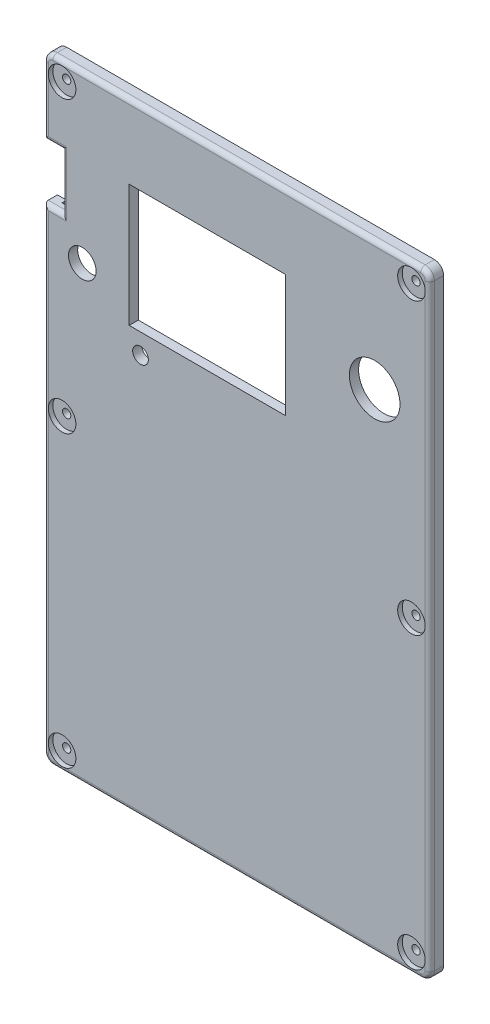
SolidWorks part; units mm, degrees
ref_plane "Front Plane" through (0, 0, 0) normal (0, 0, 1) x (1, 0, 0)
ref_plane "Top Plane" through (0, 0, 0) normal (0, 1, 0) x (1, 0, 0)
ref_plane "Right Plane" through (0, 0, 0) normal (1, 0, 0) x (0, 0, -1)
sketch "Sketch3" plane through (0, 0, 0) normal (0, 0, 1) x (1, 0, 0)
  line L9 (2.54, -170.18) -> (104.14, -170.18)
  line L10 (106.68, -167.64) -> (106.68, -2.54)
  line L11 (104.14, 0) -> (2.54, 0)
  line L17 (104.14, -10.8999) -> (104.14, -79.2701)
  line L19 (104.14, -90.9099) -> (104.14, -159.2801)
  line L21 (10.8999, -167.64) -> (95.7801, -167.64)
  line L23 (2.54, -90.9099) -> (2.54, -159.2801)
  line L25 (2.54, -10.8999) -> (2.54, -79.2701)
  line L27 (10.8999, -2.54) -> (95.7801, -2.54)
  line L43 (2.54, -79.2701) -> (2.54, -10.8999)
  line L47 (0, -2.54) -> (0, -167.64)
  line L53 (10.8999, -2.54) -> (95.7801, -2.54)
  line L55 (104.14, -10.8999) -> (104.14, -79.2701)
  line L57 (104.14, -90.9099) -> (104.14, -159.2801)
  line L59 (95.7801, -167.64) -> (10.8999, -167.64)
  line L61 (2.54, -159.2801) -> (2.54, -90.9099)
  circle A1 centre (5.08, -5.08) radius 1.143
  circle A3 centre (101.6, -5.08) radius 1.143
  arc A8 (0, -167.64) -> (2.54, -170.18) centre (2.54, -167.64) ccw
  arc A9 (104.14, -170.18) -> (106.68, -167.64) centre (104.14, -167.64) ccw
  arc A10 (106.68, -2.54) -> (104.14, 0) centre (104.14, -2.54) ccw
  arc A11 (2.54, 0) -> (0, -2.54) centre (2.54, -2.54) ccw
  circle A13 centre (101.6, -165.1) radius 1.143
  circle A15 centre (5.08, -165.1) radius 1.143
  circle A17 centre (5.08, -85.09) radius 1.143
  circle A19 centre (101.6, -85.09) radius 1.143
  arc A29 (97.8044, -4.7487) -> (95.7801, -2.54) centre (95.7801, -4.572) ccw
  arc A31 (97.8044, -4.7487) -> (101.9313, -8.8756) centre (101.6, -5.08) ccw
  arc A33 (104.14, -10.8999) -> (101.9313, -8.8756) centre (102.108, -10.8999) ccw
  arc A35 (101.9313, -81.2944) -> (101.9313, -88.8856) centre (101.6, -85.09) ccw
  arc A37 (101.9313, -81.2944) -> (104.14, -79.2701) centre (102.108, -79.2701) ccw
  arc A39 (104.14, -90.9099) -> (101.9313, -88.8856) centre (102.108, -90.9099) ccw
  arc A41 (101.9313, -161.3044) -> (104.14, -159.2801) centre (102.108, -159.2801) ccw
  arc A43 (101.9313, -161.3044) -> (97.8044, -165.4313) centre (101.6, -165.1) ccw
  arc A45 (95.7801, -167.64) -> (97.8044, -165.4313) centre (95.7801, -165.608) ccw
  arc A47 (8.8756, -165.4313) -> (10.8999, -167.64) centre (10.8999, -165.608) ccw
  arc A49 (8.8756, -165.4313) -> (4.7487, -161.3044) centre (5.08, -165.1) ccw
  arc A51 (2.54, -159.2801) -> (4.7487, -161.3044) centre (4.572, -159.2801) ccw
  arc A53 (4.7487, -88.8856) -> (2.54, -90.9099) centre (4.572, -90.9099) ccw
  arc A55 (4.7487, -88.8856) -> (4.7487, -81.2944) centre (5.08, -85.09) ccw
  arc A57 (2.54, -79.2701) -> (4.7487, -81.2944) centre (4.572, -79.2701) ccw
  arc A59 (4.7487, -8.8756) -> (8.8756, -4.7487) centre (5.08, -5.08) ccw
  arc A61 (4.7487, -8.8756) -> (2.54, -10.8999) centre (4.572, -10.8999) ccw
  arc A63 (10.8999, -2.54) -> (8.8756, -4.7487) centre (10.8999, -4.572) ccw
  arc A87 (4.7487, -8.8756) -> (2.54, -10.8999) centre (4.572, -10.8999) ccw
  arc A89 (4.7487, -8.8756) -> (8.8756, -4.7487) centre (5.08, -5.08) ccw
  arc A91 (10.8999, -2.54) -> (8.8756, -4.7487) centre (10.8999, -4.572) ccw
  arc A93 (97.8044, -4.7487) -> (95.7801, -2.54) centre (95.7801, -4.572) ccw
  arc A95 (97.8044, -4.7487) -> (101.9313, -8.8756) centre (101.6, -5.08) ccw
  arc A97 (104.14, -10.8999) -> (101.9313, -8.8756) centre (102.108, -10.8999) ccw
  arc A99 (101.9313, -81.2944) -> (104.14, -79.2701) centre (102.108, -79.2701) ccw
  arc A101 (101.9313, -81.2944) -> (101.9313, -88.8856) centre (101.6, -85.09) ccw
  arc A103 (104.14, -90.9099) -> (101.9313, -88.8856) centre (102.108, -90.9099) ccw
  arc A105 (101.9313, -161.3044) -> (104.14, -159.2801) centre (102.108, -159.2801) ccw
  arc A107 (101.9313, -161.3044) -> (97.8044, -165.4313) centre (101.6, -165.1) ccw
  arc A109 (95.7801, -167.64) -> (97.8044, -165.4313) centre (95.7801, -165.608) ccw
  arc A111 (8.8756, -165.4313) -> (10.8999, -167.64) centre (10.8999, -165.608) ccw
  arc A113 (8.8756, -165.4313) -> (4.7487, -161.3044) centre (5.08, -165.1) ccw
  arc A115 (2.54, -159.2801) -> (4.7487, -161.3044) centre (4.572, -159.2801) ccw
  arc A117 (4.7487, -88.8856) -> (2.54, -90.9099) centre (4.572, -90.9099) ccw
  arc A119 (4.7487, -88.8856) -> (4.7487, -81.2944) centre (5.08, -85.09) ccw
  arc A121 (2.54, -79.2701) -> (4.7487, -81.2944) centre (4.572, -79.2701) ccw
  dimension "D1" = 2.286
  dimension "D2" = 2.286
  dimension "D3" = 2.286
  dimension "D4" = 2.286
  dimension "D5" = 2.286
  dimension "D6" = 2.286
extrude "Boss-Extrude3" add sketch "Sketch3" along normal blind 3.81 contours L27 A63 A59 A61 L25 A57 A55 A53 L23 A51 A49 A47 L21 A45 A43 A41 L19 A39 A35 A37 L17 A33 A31 A29 | L11 A11 L47 A8 L9 A9 L10 A10 A63 L27 A29 A31 A33 L17 A37 A35 A39 L19 A41 A43 A45 L21 A47 A49 A51 L23 A53 A55 A57 L25 A61 A59 A19 A17 A15 A13 A1 A3 region at (2.1642, -168.0158, 0) region at (53.34, -85.09, 0)
sketch "Sketch7" plane through (0, 0, 0) normal (0, 0, -1) x (-1, 0, 0)
  line L0 (-106.68, -167.64) -> (-106.68, -2.54) construction
  line L1 (-104.14, -170.18) -> (-2.54, -170.18)
  line L2 (0, -167.64) -> (0, -2.54)
  line L3 (-2.54, 0) -> (-104.14, 0)
  line L4 (-2.54, -10.8999) -> (-2.54, -79.2701)
  line L5 (-2.54, -90.9099) -> (-2.54, -159.2801)
  line L6 (-95.7801, -167.64) -> (-10.8999, -167.64)
  line L7 (-104.14, -90.9099) -> (-104.14, -159.2801)
  line L9 (-95.7801, -2.54) -> (-10.8999, -2.54)
  line L11 (-104.14, -79.2701) -> (-104.14, -36.5576)
  line L13 (-106.68, -2.54) -> (-106.68, -167.64)
  line L14 (-104.14, -36.5576) -> (-104.14, -10.8999)
  line L16 (-95.7801, -2.54) -> (-10.8999, -2.54)
  line L17 (-2.54, -10.8999) -> (-2.54, -79.2701)
  line L18 (-2.54, -90.9099) -> (-2.54, -159.2801)
  line L19 (-10.8999, -167.64) -> (-95.7801, -167.64)
  line L20 (-104.14, -159.2801) -> (-104.14, -90.9099)
  line L21 (-106.68, -21.336) -> (-104.14, -21.336)
  line L22 (-104.14, -36.5576) -> (-106.68, -36.5576)
  circle A0 centre (-101.6, -5.08) radius 0.9525
  circle A1 centre (-5.08, -5.08) radius 0.9525
  arc A2 (-106.68, -167.64) -> (-104.14, -170.18) centre (-104.14, -167.64) ccw
  arc A3 (-2.54, -170.18) -> (0, -167.64) centre (-2.54, -167.64) ccw
  arc A4 (0, -2.54) -> (-2.54, 0) centre (-2.54, -2.54) ccw
  arc A5 (-104.14, 0) -> (-106.68, -2.54) centre (-104.14, -2.54) ccw
  circle A6 centre (-5.08, -165.1) radius 0.9525
  circle A7 centre (-101.6, -165.1) radius 0.9525
  circle A8 centre (-101.6, -85.09) radius 0.9525
  circle A9 centre (-5.08, -85.09) radius 0.9525
  arc A10 (-8.8756, -4.7487) -> (-10.8999, -2.54) centre (-10.8999, -4.572) ccw
  arc A11 (-8.8756, -4.7487) -> (-4.7487, -8.8756) centre (-5.08, -5.08) ccw
  arc A12 (-2.54, -10.8999) -> (-4.7487, -8.8756) centre (-4.572, -10.8999) ccw
  arc A13 (-4.7487, -81.2944) -> (-4.7487, -88.8856) centre (-5.08, -85.09) ccw
  arc A14 (-4.7487, -81.2944) -> (-2.54, -79.2701) centre (-4.572, -79.2701) ccw
  arc A15 (-2.54, -90.9099) -> (-4.7487, -88.8856) centre (-4.572, -90.9099) ccw
  arc A16 (-4.7487, -161.3044) -> (-2.54, -159.2801) centre (-4.572, -159.2801) ccw
  arc A17 (-4.7487, -161.3044) -> (-8.8756, -165.4313) centre (-5.08, -165.1) ccw
  arc A18 (-10.8999, -167.64) -> (-8.8756, -165.4313) centre (-10.8999, -165.608) ccw
  arc A19 (-97.8044, -165.4313) -> (-95.7801, -167.64) centre (-95.7801, -165.608) ccw
  arc A20 (-97.8044, -165.4313) -> (-101.9313, -161.3044) centre (-101.6, -165.1) ccw
  arc A21 (-104.14, -159.2801) -> (-101.9313, -161.3044) centre (-102.108, -159.2801) ccw
  arc A22 (-101.9313, -88.8856) -> (-104.14, -90.9099) centre (-102.108, -90.9099) ccw
  arc A23 (-101.9313, -88.8856) -> (-101.9313, -81.2944) centre (-101.6, -85.09) ccw
  arc A24 (-104.14, -79.2701) -> (-101.9313, -81.2944) centre (-102.108, -79.2701) ccw
  arc A25 (-101.9313, -8.8756) -> (-97.8044, -4.7487) centre (-101.6, -5.08) ccw
  arc A26 (-101.9313, -8.8756) -> (-104.14, -10.8999) centre (-102.108, -10.8999) ccw
  arc A27 (-95.7801, -2.54) -> (-97.8044, -4.7487) centre (-95.7801, -4.572) ccw
  arc A28 (-101.9313, -8.8756) -> (-104.14, -10.8999) centre (-102.108, -10.8999) ccw
  arc A29 (-101.9313, -8.8756) -> (-97.8044, -4.7487) centre (-101.6, -5.08) ccw
  arc A30 (-95.7801, -2.54) -> (-97.8044, -4.7487) centre (-95.7801, -4.572) ccw
  arc A31 (-8.8756, -4.7487) -> (-10.8999, -2.54) centre (-10.8999, -4.572) ccw
  arc A32 (-8.8756, -4.7487) -> (-4.7487, -8.8756) centre (-5.08, -5.08) ccw
  arc A33 (-2.54, -10.8999) -> (-4.7487, -8.8756) centre (-4.572, -10.8999) ccw
  arc A34 (-4.7487, -81.2944) -> (-2.54, -79.2701) centre (-4.572, -79.2701) ccw
  arc A35 (-4.7487, -81.2944) -> (-4.7487, -88.8856) centre (-5.08, -85.09) ccw
  arc A36 (-2.54, -90.9099) -> (-4.7487, -88.8856) centre (-4.572, -90.9099) ccw
  arc A37 (-4.7487, -161.3044) -> (-2.54, -159.2801) centre (-4.572, -159.2801) ccw
  arc A38 (-4.7487, -161.3044) -> (-8.8756, -165.4313) centre (-5.08, -165.1) ccw
  arc A39 (-10.8999, -167.64) -> (-8.8756, -165.4313) centre (-10.8999, -165.608) ccw
  arc A40 (-97.8044, -165.4313) -> (-95.7801, -167.64) centre (-95.7801, -165.608) ccw
  arc A41 (-97.8044, -165.4313) -> (-101.9313, -161.3044) centre (-101.6, -165.1) ccw
  arc A42 (-104.14, -159.2801) -> (-101.9313, -161.3044) centre (-102.108, -159.2801) ccw
  arc A43 (-101.9313, -88.8856) -> (-104.14, -90.9099) centre (-102.108, -90.9099) ccw
  arc A44 (-101.9313, -88.8856) -> (-101.9313, -81.2944) centre (-101.6, -85.09) ccw
  arc A45 (-104.14, -79.2701) -> (-101.9313, -81.2944) centre (-102.108, -79.2701) ccw
extrude "Cut-Extrude9" cut sketch "Sketch7" against normal blind 1.27 contours L9 A27 A25 A26 L14 L11 A24 A23 A22 L7 A21 A20 A19 L6 A18 A17 A16 L5 A15 A13 A14 L4 A12 A11 A10 region at (53.34, -85.09, 0)
sketch "Sketch10" plane through (0, 0, 3.81) normal (0, 0, 1) x (1, 0, 0)
  line L0 (0, -2.54) -> (0, -21.336)
  line L1 (2.54, -170.18) -> (104.14, -170.18)
  line L2 (106.68, -167.64) -> (106.68, -2.54)
  line L3 (104.14, 0) -> (2.54, 0)
  line L4 (104.14, -10.8999) -> (104.14, -79.2701)
  line L5 (104.14, -90.9099) -> (104.14, -159.2801)
  line L6 (10.8999, -167.64) -> (95.7801, -167.64)
  line L7 (2.54, -90.9099) -> (2.54, -159.2801)
  line L8 (2.54, -36.576) -> (2.54, -79.2701)
  line L9 (10.8999, -2.54) -> (95.7801, -2.54)
  line L10 (2.54, -10.8999) -> (2.54, -21.336)
  line L11 (2.54, -79.2701) -> (2.54, -36.576)
  line L12 (2.54, -36.576) -> (0, -36.576)
  line L13 (0, -36.576) -> (0, -167.64)
  line L14 (0, -21.336) -> (2.54, -21.336)
  line L15 (2.54, -21.336) -> (2.54, -10.8999)
  line L16 (10.8999, -2.54) -> (95.7801, -2.54)
  line L17 (104.14, -10.8999) -> (104.14, -79.2701)
  line L18 (104.14, -90.9099) -> (104.14, -159.2801)
  line L19 (95.7801, -167.64) -> (10.8999, -167.64)
  line L20 (2.54, -159.2801) -> (2.54, -90.9099)
  line L22 (0, -21.336) -> (5.08, -21.336)
  line L23 (0, -21.336) -> (0, -36.576)
  line L24 (0, -36.576) -> (5.08, -36.576)
  line L25 (5.08, -21.336) -> (5.08, -36.576)
  circle A0 centre (5.08, -5.08) radius 0.9525
  circle A1 centre (101.6, -5.08) radius 0.9525
  arc A2 (0, -167.64) -> (2.54, -170.18) centre (2.54, -167.64) ccw
  arc A3 (104.14, -170.18) -> (106.68, -167.64) centre (104.14, -167.64) ccw
  arc A4 (106.68, -2.54) -> (104.14, 0) centre (104.14, -2.54) ccw
  arc A5 (2.54, 0) -> (0, -2.54) centre (2.54, -2.54) ccw
  circle A6 centre (101.6, -165.1) radius 0.9525
  circle A7 centre (5.08, -165.1) radius 0.9525
  circle A8 centre (5.08, -85.09) radius 0.9525
  circle A9 centre (101.6, -85.09) radius 0.9525
  arc A10 (97.8044, -4.7487) -> (95.7801, -2.54) centre (95.7801, -4.572) ccw
  arc A11 (97.8044, -4.7487) -> (101.9313, -8.8756) centre (101.6, -5.08) ccw
  arc A12 (104.14, -10.8999) -> (101.9313, -8.8756) centre (102.108, -10.8999) ccw
  arc A13 (101.9313, -81.2944) -> (101.9313, -88.8856) centre (101.6, -85.09) ccw
  arc A14 (101.9313, -81.2944) -> (104.14, -79.2701) centre (102.108, -79.2701) ccw
  arc A15 (104.14, -90.9099) -> (101.9313, -88.8856) centre (102.108, -90.9099) ccw
  arc A16 (101.9313, -161.3044) -> (104.14, -159.2801) centre (102.108, -159.2801) ccw
  arc A17 (101.9313, -161.3044) -> (97.8044, -165.4313) centre (101.6, -165.1) ccw
  arc A18 (95.7801, -167.64) -> (97.8044, -165.4313) centre (95.7801, -165.608) ccw
  arc A19 (8.8756, -165.4313) -> (10.8999, -167.64) centre (10.8999, -165.608) ccw
  arc A20 (8.8756, -165.4313) -> (4.7487, -161.3044) centre (5.08, -165.1) ccw
  arc A21 (2.54, -159.2801) -> (4.7487, -161.3044) centre (4.572, -159.2801) ccw
  arc A22 (4.7487, -88.8856) -> (2.54, -90.9099) centre (4.572, -90.9099) ccw
  arc A23 (4.7487, -88.8856) -> (4.7487, -81.2944) centre (5.08, -85.09) ccw
  arc A24 (2.54, -79.2701) -> (4.7487, -81.2944) centre (4.572, -79.2701) ccw
  arc A25 (4.7487, -8.8756) -> (8.8756, -4.7487) centre (5.08, -5.08) ccw
  arc A26 (4.7487, -8.8756) -> (2.54, -10.8999) centre (4.572, -10.8999) ccw
  arc A27 (10.8999, -2.54) -> (8.8756, -4.7487) centre (10.8999, -4.572) ccw
  arc A28 (4.7487, -8.8756) -> (2.54, -10.8999) centre (4.572, -10.8999) ccw
  arc A29 (4.7487, -8.8756) -> (8.8756, -4.7487) centre (5.08, -5.08) ccw
  arc A30 (10.8999, -2.54) -> (8.8756, -4.7487) centre (10.8999, -4.572) ccw
  arc A31 (97.8044, -4.7487) -> (95.7801, -2.54) centre (95.7801, -4.572) ccw
  arc A32 (97.8044, -4.7487) -> (101.9313, -8.8756) centre (101.6, -5.08) ccw
  arc A33 (104.14, -10.8999) -> (101.9313, -8.8756) centre (102.108, -10.8999) ccw
  arc A34 (101.9313, -81.2944) -> (104.14, -79.2701) centre (102.108, -79.2701) ccw
  arc A35 (101.9313, -81.2944) -> (101.9313, -88.8856) centre (101.6, -85.09) ccw
  arc A36 (104.14, -90.9099) -> (101.9313, -88.8856) centre (102.108, -90.9099) ccw
  arc A37 (101.9313, -161.3044) -> (104.14, -159.2801) centre (102.108, -159.2801) ccw
  arc A38 (101.9313, -161.3044) -> (97.8044, -165.4313) centre (101.6, -165.1) ccw
  arc A39 (95.7801, -167.64) -> (97.8044, -165.4313) centre (95.7801, -165.608) ccw
  arc A40 (8.8756, -165.4313) -> (10.8999, -167.64) centre (10.8999, -165.608) ccw
  arc A41 (8.8756, -165.4313) -> (4.7487, -161.3044) centre (5.08, -165.1) ccw
  arc A42 (2.54, -159.2801) -> (4.7487, -161.3044) centre (4.572, -159.2801) ccw
  arc A43 (4.7487, -88.8856) -> (2.54, -90.9099) centre (4.572, -90.9099) ccw
  arc A44 (4.7487, -88.8856) -> (4.7487, -81.2944) centre (5.08, -85.09) ccw
  arc A45 (2.54, -79.2701) -> (4.7487, -81.2944) centre (4.572, -79.2701) ccw
  line M9 (0, -2.54) -> (0, -167.64)
  dimension "D1" = 5.08
extrude "Cut-Extrude10" cut sketch "Sketch10" against normal through all contours L25 L22 L14 L12 L24 M9 region at (2.54, -28.956, 3.81)
sketch "Sketch11" plane through (0, 0, 3.81) normal (0, 0, 1) x (1, 0, 0)
  line L0 (104.14, 0) -> (2.54, 0) construction
  line L1 (3.81, -10.16) -> (72.39, -10.16)
  line L2 (3.81, -10.16) -> (3.81, -63.5)
  line L3 (3.81, -63.5) -> (72.39, -63.5)
  line L4 (72.39, -10.16) -> (72.39, -63.5)
  line L5 (0, -2.54) -> (0, -21.336) construction
  line L6 (106.68, -167.64) -> (106.68, -2.54) construction
  line L7 (23.622, -20.32) -> (66.802, -20.32)
  line L8 (23.622, -20.32) -> (23.622, -54.102)
  line L9 (23.622, -54.102) -> (66.802, -54.102)
  line L10 (66.802, -20.32) -> (66.802, -54.102)
  circle A0 centre (10.668, -45.72) radius 3.81
  circle A1 centre (26.7462, -59.69) radius 2.159
  circle A2 centre (91.44, -35.56) radius 6.985
  dimension "D7" = 7.62
  dimension "D14" = 4.318
  dimension "D17" = 13.97
  dimension "D1" = 68.58
  dimension "D2" = 53.34
  dimension "D3" = 10.16
  dimension "D4" = 3.81
  dimension "D5" = 35.56
  dimension "D6" = 6.858
  dimension "D8" = 43.18
  dimension "D9" = 33.782
  dimension "D10" = 10.16
  dimension "D11" = 19.812
  dimension "D12" = 3.81
  dimension "D13" = 22.9362
  dimension "D15" = 15.24
  dimension "D16" = 35.56
extrude "Cut-Extrude11" cut sketch "Sketch11" against normal through all contours L10 L7 L8 L9 | A0 | A1 | A2 region at (45.212, -37.211, 3.81) region at (10.668, -45.72, 3.81) region at (26.7462, -59.69, 3.81) region at (91.44, -35.56, 3.81)
sketch "Sketch12" plane through (0, 0, 3.81) normal (0, 0, 1) x (1, 0, 0)
  circle A0 centre (5.08, -5.08) radius 3.81
  circle A1 centre (101.6, -5.08) radius 3.81
  circle A2 centre (101.6, -85.09) radius 3.81
  circle A3 centre (101.6, -165.1) radius 3.81
  circle A4 centre (5.08, -165.1) radius 3.81
  circle A5 centre (5.08, -85.09) radius 3.81
  dimension "D1" = 7.62
  dimension "D2" = 7.62
  dimension "D3" = 7.62
  dimension "D4" = 7.62
  dimension "D5" = 7.62
  dimension "D6" = 7.62
extrude "Cut-Extrude12" cut sketch "Sketch12" against normal blind 1.27
fillet "Fillet1" radius 1.27 12 edges at (2.54, -36.576, 3.81) (2.54, -21.336, 3.81) (5.08, -28.956, 3.81) (0.7439, -0.7439, 3.81) (0, -11.938, 3.81) (53.34, 0, 3.81) (105.9361, -0.7439, 3.81) (105.9361, -169.4361, 3.81) (106.68, -85.09, 3.81) (0.7439, -169.4361, 3.81) (53.34, -170.18, 3.81) (0, -102.108, 3.81)
